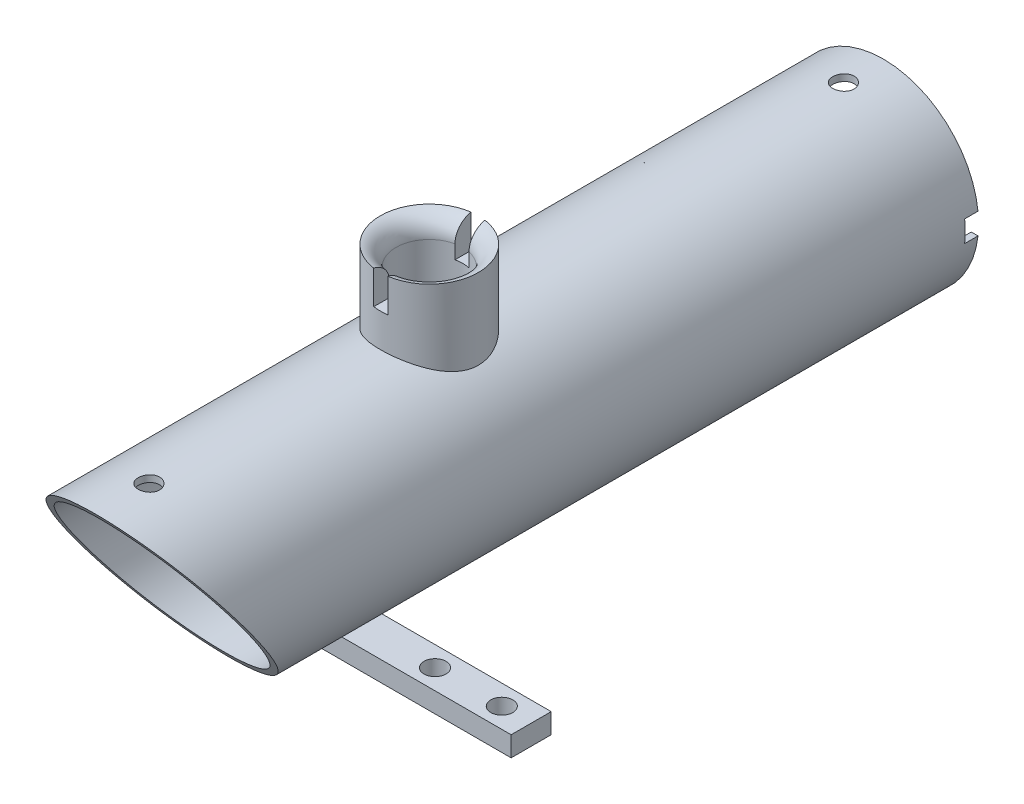
SolidWorks part; units mm, degrees
ref_plane "Front Plane" through (0, 0, 0) normal (0, 0, 1) x (1, 0, 0)
ref_plane "Top Plane" through (0, 0, 0) normal (0, 1, 0) x (1, 0, 0)
ref_plane "Right Plane" through (0, 0, 0) normal (1, 0, 0) x (0, 0, -1)
sketch "Sketch4" plane through (0, 0, 0) normal (0, 0, 1) x (1, 0, 0)
  circle A0 centre (0, 0) radius 14.25
  circle A1 centre (0, 0) radius 13.25
  dimension "D1" = 26.5
  dimension "D2" = 1
extrude "Boss-Extrude3" add sketch "Sketch4" along normal blind 118
sketch "Sketch5" plane through (0, 0, 118) normal (0, 0, 1) x (1, 0, 0)
  circle A0 centre (0, 0) radius 14.25 construction
  point P0 (0, 14.25)
  point P1 (14.25, 0)
  point P4 (-14.25, 0)
  point P5 (0, -14.25)
ref_plane "Plane1" through (0, 14.25, 118) normal (0, 1, 0) x (1, 0, 0)
sketch "Sketch6" plane through (0, 14.25, 118) normal (0, 1, 0) x (1, 0, 0)
  line L0 (-14.25, 0) -> (14.25, 0) construction
  circle A0 centre (0, 50) radius 5
  circle A1 centre (0, 50) radius 7.35
  dimension "D1" = 10
  dimension "D2" = 2.35
  dimension "D3" = 50
extrude "Boss-Extrude4" add sketch "Sketch6" along normal blind 10 and the other way blind 4
sketch "Sketch7" plane through (0, 24.25, 0) normal (0, 1, 0) x (1, 0, 0)
  circle A0 centre (0, -68) radius 5
  circle A1 centre (0, -68) radius 5 construction
extrude "Cut-Extrude1" cut sketch "Sketch7" against normal blind 20
sketch "Sketch8" plane through (0, 0, 118) normal (0, 0, 1) x (1, 0, 0)
  circle A0 centre (0, 0) radius 13.25
extrude "Cut-Extrude2" cut sketch "Sketch8" against normal up to surface (118 mm away) up to face at (14.25, 0, 0)
sketch "Sketch11" plane through (0, 14.25, 118) normal (0, 1, 0) x (1, 0, 0)
  line L0 (-14.25, 0) -> (14.25, 0) construction
  line L1 (13.25, 118) -> (-13.25, 118) construction
  circle A0 centre (0, 8) radius 1.6
  circle A1 centre (0, 112) radius 1.6
  dimension "D1" = 3.2
  dimension "D2" = 8
  dimension "D3" = 6
extrude "Cut-Extrude5" cut sketch "Sketch11" against normal blind 13
ref_plane "Plane5" through (0, -14.25, 118) normal (0, -1, 0) x (-1, 0, 0)
sketch "Sketch15" plane through (0, -14.25, 118) normal (0, -1, 0) x (-1, 0, 0)
  line L5 (0, 65) -> (0, 0) construction
  line L6 (14.25, 0) -> (14.25, 118) construction
  line L7 (14.25, 28) -> (-34.25, 28)
  line L13 (14.25, 28) -> (14.25, 34)
  line L14 (14.25, 34) -> (-34.25, 34)
  line L15 (-34.25, 28) -> (-34.25, 34)
  line L16 (-14.25, 118) -> (-14.25, 0) construction
  line L17 (-14.25, 0) -> (14.25, 0) construction
  line L18 (-34.25, 31) -> (14.25, 31) construction
  circle A2 centre (-19.85, 31) radius 1.65
  circle A3 centre (-29.85, 31) radius 1.65
  point P0 (0, 65)
  point P15 (0, 65)
  point P16 (0, 22.5)
  dimension "D4" = 3.3
  dimension "D5" = 10
  dimension "D6" = 5.6
  dimension "D1" = 20
  dimension "D2" = 6
  dimension "D3" = 28
fillet "Fillet2" radius 3 1 edges at (-5, 24.25, 68)
sketch "Sketch20" plane through (0, 14.25, 118) normal (0, 1, 0) x (1, 0, 0)
  line L1 (-1.05, 57.35) -> (1.05, 57.35)
  line L2 (-1.05, 57.35) -> (-1.05, 54.35)
  line L3 (-1.05, 54.35) -> (1.05, 54.35)
  line L4 (1.05, 57.35) -> (1.05, 54.35)
  line L5 (-1.05, 45.65) -> (1.05, 45.65)
  line L6 (-1.05, 45.65) -> (-1.05, 42.65)
  line L7 (-1.05, 42.65) -> (1.05, 42.65)
  line L8 (1.05, 45.65) -> (1.05, 42.65)
  circle A2 centre (0, 50) radius 7.35 construction
  circle A3 centre (0, 50) radius 4.7474
  circle A4 centre (0, 50) radius 5 construction
  point P14 (0, 45.65)
  point P15 (0, 54.35)
  dimension "D1" = 2.1
  dimension "D2" = 3
extrude "Boss-Extrude8" add sketch "Sketch15" against normal blind 3
sketch "Sketch27" plane through (0, 0, 0) normal (0, 0, -1) x (-1, 0, 0)
  circle A0 centre (0, 0) radius 13.25
extrude "Cut-Extrude15" cut sketch "Sketch27" against normal up to surface (118 mm away) up to face at (14.25, 0, 118)
sketch "Sketch28" plane through (-14.25, 0, 0) normal (-1, 0, 0) x (0, 0, 1)
  line L0 (118, 14.25) -> (98.0441, -14.25)
  line L2 (98.0441, -14.25) -> (118, -14.25)
  line L3 (118, -14.25) -> (118, 14.25)
  dimension "D1" = 35
extrude "Cut-Extrude16" cut sketch "Sketch28" against normal blind 32
sketch "Sketch29" plane through (0, 0, 0) normal (0, 0, -1) x (-1, 0, 0)
  line L1 (-17.6299, -1.6) -> (17.6299, -1.6)
  line L2 (-17.6299, -1.6) -> (-17.6299, 1.6)
  line L3 (-17.6299, 1.6) -> (17.6299, 1.6)
  line L4 (17.6299, -1.6) -> (17.6299, 1.6)
  line L5 (-17.6299, -1.6) -> (17.6299, 1.6) construction
  line L6 (-17.6299, 1.6) -> (17.6299, -1.6) construction
  point P0 (0, 0)
  dimension "D1" = 3.2
extrude "Cut-Extrude17" cut sketch "Sketch29" against normal blind 2
extrude "Cut-Extrude18" cut sketch "Sketch20" along normal blind 10 from offset 5 contours A3 L4 L1 L2 | A3 L6 L7 L8 region at (0, 14.25, 61.971) region at (0, 14.25, 74.029)
